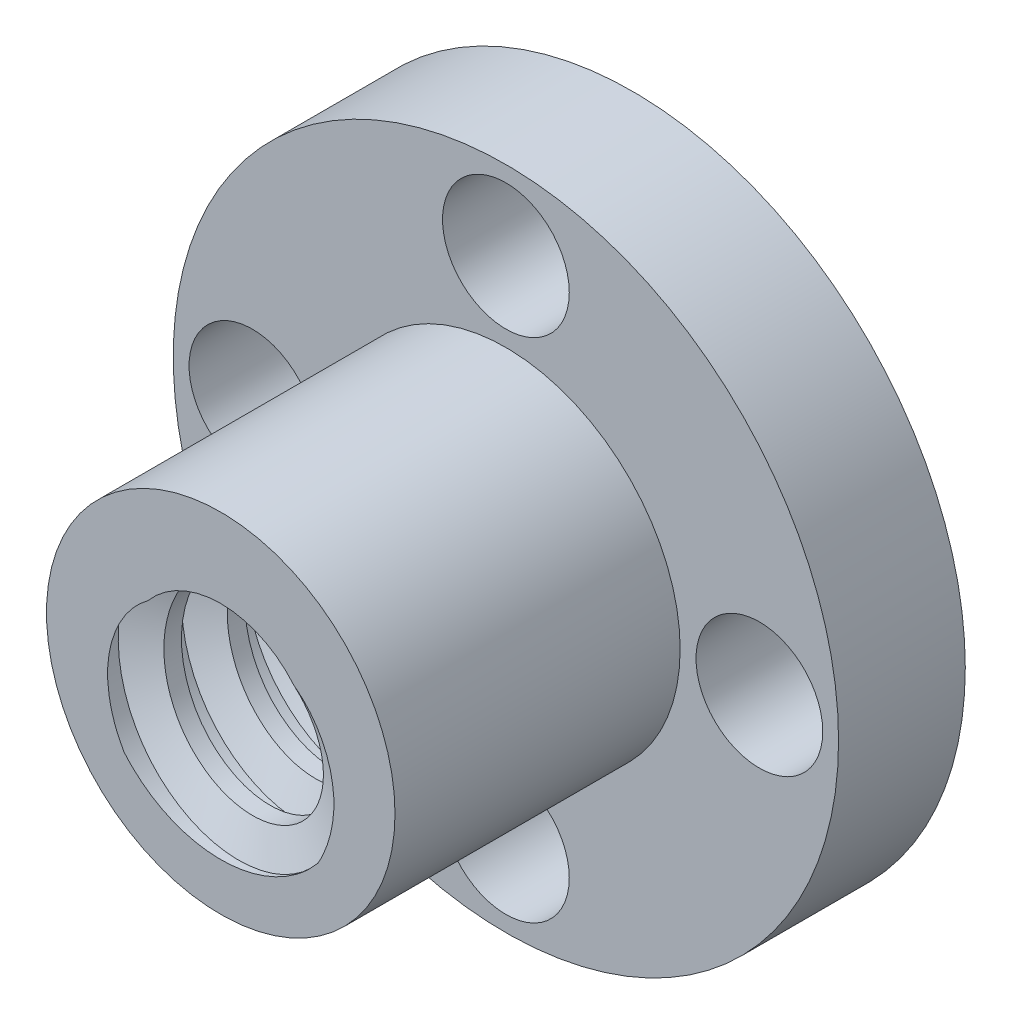
SolidWorks part; units mm, degrees
ref_plane "Alzado" through (0, 0, 0) normal (0, 0, 1) x (1, 0, 0)
ref_plane "Planta" through (0, 0, 0) normal (0, 1, 0) x (1, 0, 0)
ref_plane "Vista lateral" through (0, 0, 0) normal (1, 0, 0) x (0, 0, -1)
sketch "Croquis1" plane through (0, 0, 0) normal (0, 0, 1) x (1, 0, 0)
  circle A0 centre (0, 0) radius 10.5
  circle A1 centre (0, 0) radius 3
  circle A2 centre (0, 0) radius 8 construction
  circle A3 centre (0, 8) radius 2
  circle A4 centre (8, 0) radius 2
  circle A5 centre (0, -8) radius 2
  circle A6 centre (-8, 0) radius 2
  point P16 (0, 0)
  dimension "D1" = 21
  dimension "D2" = 6
  dimension "D3" = 16
  dimension "D4" = 4
  dimension "D5" = 4
extrude "Saliente-Extruir1" add sketch "Croquis1" along normal blind 4
ref_plane "Plano1" through (0, 0, 4) normal (0, 0, 1) x (1, 0, 0)
sketch "Croquis2" plane through (0, 0, 4) normal (0, 0, 1) x (1, 0, 0)
  circle A0 centre (0, 0) radius 3
  circle A1 centre (0, 0) radius 5.5
  dimension "D1" = 11
  dimension "D2" = 6
extrude "Saliente-Extruir2" add sketch "Croquis2" along normal blind 9
ref_plane "Plano2" through (0, 0, 0) normal (1, 0, 0) x (0, 0, -1)
ref_plane "Plano3" through (0, 0, -2) normal (0, 0, -1) x (-1, 0, 0)
sketch "Croquis3" plane through (0, 0, -2) normal (0, 0, -1) x (-1, 0, 0)
  line L0 (0, 0) -> (0, 3.9848) construction
  line L1 (0, 8.6474) -> (0, -8.6474) construction
  line L2 (0, 0) -> (3.8876, 0) construction
  circle A0 centre (0, 0) radius 3
  point P3 (0, 3)
  dimension "D1" = 6
sketch "Croquis5" plane through (0, 0, -2) normal (0, 0, -1) x (-1, 0, 0)
  point P0 (0, 3)
sketch "Croquis6" plane through (0, 0, 0) normal (1, 0, 0) x (0, 0, -1)
  line L0 (1.2774, 3) -> (2.7226, 3)
  line L1 (2.7226, 3) -> (2.2774, 4)
  line L2 (2.2774, 4) -> (1.7226, 4)
  line L3 (1.7226, 4) -> (1.2774, 3)
  line L4 (2, 0) -> (2, 3.9848) construction
  line L5 (2, 3) -> (2, 4.6238) construction
  line L6 (1.5, 3.5) -> (2.5, 3.5) construction
  point P0 (2, 3)
  point P4 (2, 4)
  dimension "D1" = 1
  dimension "D2" = 24
  dimension "D3" = 1
curve "Hélice/Espiral1" pitch 2 height 18 radius 3 centre (0, 0, -2) axis (0, 0, 1) start towards (0, 1, 0)
sweep "Cortar-Barrer1" cut profiles "Croquis6" path "Hélice/Espiral1" align with end faces yes
